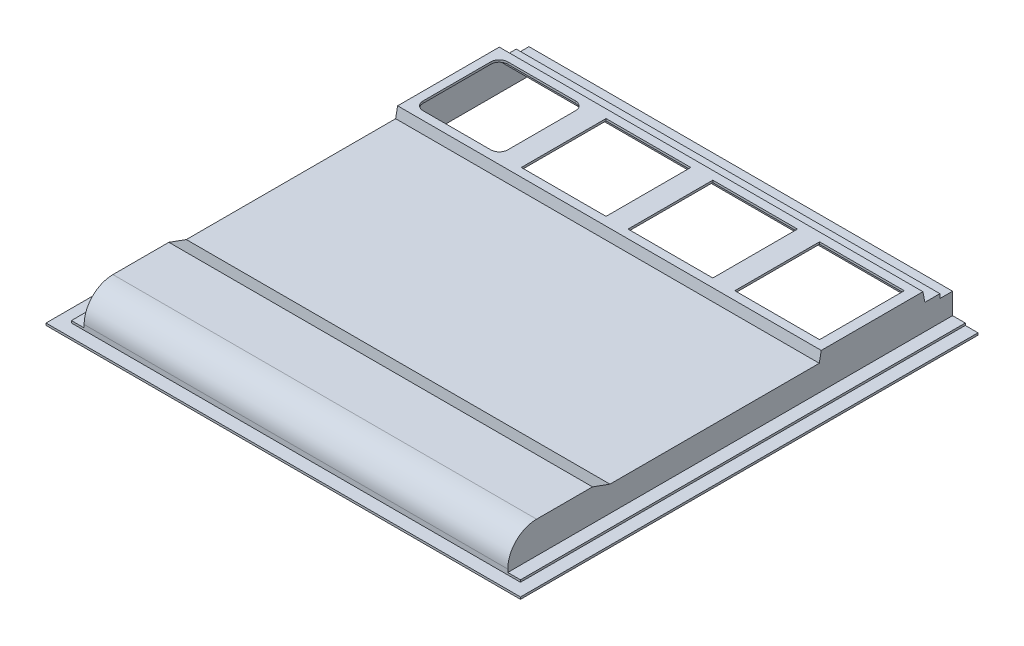
SolidWorks part; units mm, degrees
material "ABS"
ref_plane "Front Plane" through (0, 0, 0) normal (0, 0, 1) x (1, 0, 0)
ref_plane "Top Plane" through (0, 0, 0) normal (0, 1, 0) x (1, 0, 0)
ref_plane "Right Plane" through (0, 0, 0) normal (1, 0, 0) x (0, 0, -1)
sketch "Sketch1" plane through (0, 0, 0) normal (0, 1, 0) x (1, 0, 0)
  line L1 (-355.6, 342.9) -> (355.6, 342.9)
  line L2 (-355.6, 342.9) -> (-355.6, -342.9)
  line L3 (-355.6, -342.9) -> (355.6, -342.9)
  line L4 (355.6, 342.9) -> (355.6, -342.9)
  line L5 (-355.6, 342.9) -> (355.6, -342.9) construction
  line L6 (-355.6, -342.9) -> (355.6, 342.9) construction
  point P0 (0, 0)
  dimension "D1" = 711.2
  dimension "D2" = 685.8
extrude "Boss-Extrude1" add sketch "Sketch1" along normal blind 3.175
sketch "Sketch2" plane through (0, 3.175, 0) normal (0, 1, 0) x (1, 0, 0)
  line L0 (355.6, 342.9) -> (-355.6, 342.9) construction
  line L1 (-317.5, 342.9) -> (317.5, 342.9)
  line L2 (-317.5, 342.9) -> (-317.5, -323.85)
  line L3 (-317.5, -323.85) -> (317.5, -323.85)
  line L4 (317.5, 342.9) -> (317.5, -323.85)
  line L5 (-355.6, -342.9) -> (355.6, -342.9) construction
  line L6 (0, 0) -> (0, -444.336) construction
  line L7 (-355.6, 342.9) -> (-355.6, -342.9) construction
  dimension "D1" = 19.05
  dimension "D2" = 38.1
extrude "Boss-Extrude2" add sketch "Sketch2" along normal blind 50.8
sketch "Sketch3" plane through (0, 0, 0) normal (1, 0, 0) x (0, 0, -1)
  line L0 (-196.85, 53.975) -> (-170.6803, 44.45)
  line L1 (-323.85, 53.975) -> (342.9, 53.975) construction
  line L2 (-170.6803, 44.45) -> (342.9, 44.45)
  line L3 (342.9, 53.975) -> (342.9, 3.175) construction
  line L4 (342.9, 44.45) -> (342.9, 53.975)
  line L5 (342.9, 53.975) -> (-196.85, 53.975)
  line L6 (-323.85, 53.975) -> (-323.85, 3.175) construction
  line L7 (-342.9, 0) -> (342.9, 0) construction
  dimension "D1" = 127
  dimension "D2" = 44.45
  dimension "D3" = 160
extrude "Cut-Extrude1" cut sketch "Sketch3" against normal through all and the other way through all
sketch "Sketch4" plane through (0, 3.175, 0) normal (0, 1, 0) x (1, 0, 0)
  line L0 (-317.5, -323.85) -> (317.5, -323.85) construction
  line L1 (-317.5, 342.9) -> (-336.55, 342.9)
  line L2 (-317.5, 342.9) -> (-317.5, -323.85)
  line L3 (-317.5, -323.85) -> (-336.55, -323.85)
  line L4 (-336.55, 342.9) -> (-336.55, -323.85)
  line L5 (-317.5, -323.85) -> (317.5, -323.85) construction
  dimension "D1" = 19.05
extrude "Boss-Extrude3" add sketch "Sketch4" along normal blind 3.175
mirror "Mirror1" about plane through (0, 0, 0) normal (1, 0, 0) of "Boss-Extrude3"
sketch "Sketch5" plane through (0, 0, -342.9) normal (0, 0, -1) x (-1, 0, 0)
  line L2 (-317.5, 44.45) -> (-317.5, 6.35) construction
  line L3 (-317.5, 38.1) -> (0, 38.1)
  line L4 (0, 38.1) -> (0, 44.45)
  line L5 (317.5, 44.45) -> (-317.5, 44.45) construction
  line L6 (0, 44.45) -> (-317.5, 44.45)
  line L7 (-317.5, 44.45) -> (-317.5, 38.1)
  line L8 (-355.6, 0) -> (355.6, 0) construction
  dimension "D1" = 38.1
extrude "Cut-Extrude2" cut sketch "Sketch5" against normal blind 19.05
mirror "Mirror2" about plane through (0, 0, 0) normal (1, 0, 0) of "Cut-Extrude2"
fillet "Fillet1" radius 43.18 1 edges at (0, 53.975, 323.85)
sketch "Sketch6" plane through (0, 44.45, 0) normal (0, 1, 0) x (1, 0, 0)
  line L0 (-317.5, -323.85) -> (-317.5, 342.9) construction
  line L1 (-317.5, 298.45) -> (317.5, 298.45)
  line L2 (-317.5, 298.45) -> (-317.5, 146.05)
  line L3 (-317.5, 146.05) -> (317.5, 146.05)
  line L4 (317.5, 298.45) -> (317.5, 146.05)
  line L5 (317.5, 323.85) -> (317.5, -170.6803) construction
  line L6 (317.5, 323.85) -> (-317.5, 323.85) construction
  dimension "D1" = 25.4
  dimension "D2" = 152.4
extrude "Boss-Extrude4" add sketch "Sketch6" along normal blind 15.24
draft "Draft2" type of draft neutral plane draft angle 11 faces to draft 2 face at (0, 52.07, -146.05) face at (0, 52.07, -298.45) neutral plane through (0, 59.69, 0) neutral plane normal (0, 1, 0) parameters "D1"=11
shell "Shell1" thickness 3.175 removed face at (0, 0, 0) removed face at (0, 9.525, -342.9)
sketch "Sketch7" plane through (0, 59.69, 0) normal (0, 1, 0) x (1, 0, 0)
  line L0 (-317.5, 146.05) -> (317.5, 146.05) construction
  line L1 (-304.8, 285.75) -> (-177.8, 285.75)
  line L2 (-304.8, 285.75) -> (-304.8, 158.75)
  line L3 (-304.8, 158.75) -> (-177.8, 158.75)
  line L4 (-177.8, 285.75) -> (-177.8, 158.75)
  line L5 (-317.5, 298.45) -> (-317.5, 146.05) construction
  dimension "D1" = 127
  dimension "D2" = 127
  dimension "D3" = 12.7
  dimension "D4" = 12.7
extrude "Cut-Extrude3" cut sketch "Sketch7" against normal blind 25.4
pattern_linear "LPattern1" count 4 spacing 160.02 along (1, 0, 0) of "Cut-Extrude3"
fillet "Fillet2" radius 12.7 4 edges at (-177.8, 58.1025, -158.75) (-304.8, 58.1025, -158.75) (-304.8, 58.1025, -285.75) (-177.8, 58.1025, -285.75)
